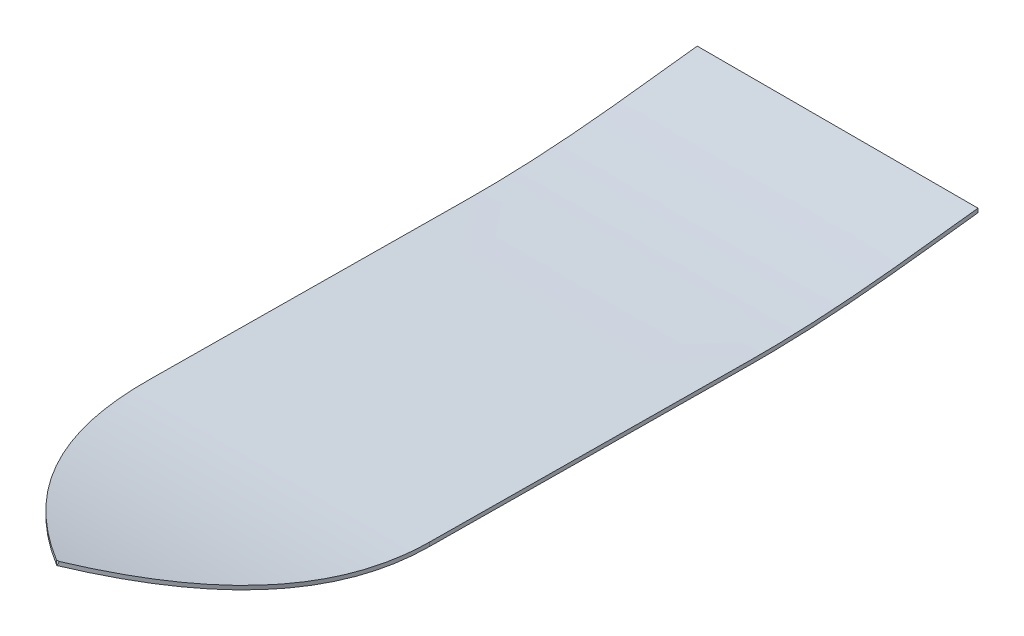
SolidWorks part; units mm, degrees
ref_plane "Front Plane" through (0, 0, 0) normal (0, 0, 1) x (1, 0, 0)
ref_plane "Top Plane" through (0, 0, 0) normal (0, 1, 0) x (1, 0, 0)
ref_plane "Right Plane" through (0, 0, 0) normal (1, 0, 0) x (0, 0, -1)
sketch "Sketch1" plane through (0, 0, 0) normal (1, 0, 0) x (0, 0, -1)
  line L6 (-3044.2698, 164.4803) -> (-3050.7389, 140.3318)
  line L7 (1954.9582, 71.8051) -> (1957.9009, 46.9789)
  spline S0 degree 3 poles (-3044.2698, 164.4803) (-2812.3217, 102.3436) (-2472.36, 36.8584) (-1994.9412, -9.8893) (-1747.6762, -21.1854) (-1597.5125, -23.4676) (-1563.2422, -23.7855) (-1460.4237, -24.7287) (-1282.2019, -26.3591) (-1001.1607, -28.9313) (-589.881, -32.6958) (-206.0199, -36.2092) (164.1318, -39.5971) (337.2119, -41.1813) (458.8794, -42.2934) (493.1569, -42.6094) (566.4691, -43.0811) (687.4943, -42.0008) (1179.1806, -25.7469) (1562.5379, 25.2909) (1954.9582, 71.8051) knots 0 0 0 0 0.15625 0.21875 0.289062 0.300781 0.304688 0.308594 0.359375 0.40625 0.46875 0.59375 0.625 0.679688 0.692383 0.694336 0.699219 0.734375 0.765625 1 1 1 1
  spline S1 degree 1 poles (-3050.7389, 140.3318) (1957.9009, 46.9789) knots 0 0 1 1 construction
  spline S2 degree 3 poles (-3050.7389, 140.3318) (-3039.0666, 137.2049) (-3015.7221, 131.043) (-2968.7594, 119.0132) (-2909.6691, 104.561) (-2838.1023, 88.1439) (-2741.8165, 67.4919) (-2619.8339, 43.9951) (-2470.8578, 19.5074) (-2319.285, -1.2734) (-2165.1165, -18.3484) (-2008.3529, -31.7191) (-1875.5546, -39.7757) (-1768.0188, -44.3698) (-1700.269, -46.4717) (-1645.7441, -47.6872) (-1604.6906, -48.3776) (-1563.4486, -48.7918) (-1522.3501, -49.1597) (-1481.2146, -49.5391) (-1426.3799, -50.0406) (-1330.4129, -50.9195) (-1193.3203, -52.1735) (-1028.8081, -53.6794) (-864.2963, -55.1851) (-699.7844, -56.6909) (-535.2725, -58.1966) (-370.7606, -59.7024) (-206.2488, -61.2081) (-41.7369, -62.7139) (95.3563, -63.9687) (205.031, -64.9725) (287.2863, -65.7252) (355.8337, -66.3524) (410.6675, -66.8536) (444.9472, -67.1675) (472.3507, -67.4179) (492.9632, -67.6114) (513.4929, -67.735) (540.7008, -67.8206) (574.4475, -67.7776) (627.8916, -67.3981) (693.7232, -66.3556) (771.325, -64.2438) (847.6955, -61.3194) (948.1, -56.4017) (1071.349, -48.4663) (1216.9541, -36.4721) (1361.5858, -22.3963) (1482.4051, -9.2564) (1579.9013, 1.9075) (1653.6106, 10.5581) (1728.0741, 19.438) (1790.8946, 26.9889) (1841.6962, 33.0963) (1880.0886, 37.7039) (1912.3506, 41.562) (1938.3133, 44.6544) (1951.3785, 46.2058) (1957.9009, 46.9789) knots 0 0 0 0 0.007812 0.015625 0.03125 0.046875 0.0625 0.09375 0.125 0.15625 0.1875 0.21875 0.25 0.265625 0.28125 0.289062 0.296875 0.304688 0.3125 0.320312 0.328125 0.34375 0.375 0.40625 0.4375 0.46875 0.5 0.53125 0.5625 0.59375 0.625 0.640625 0.65625 0.671875 0.679688 0.6875 0.691406 0.695312 0.699219 0.703125 0.710938 0.71875 0.734375 0.75 0.765625 0.78125 0.8125 0.84375 0.875 0.90625 0.921875 0.9375 0.953125 0.96875 0.976562 0.984375 0.992188 0.996094 1 1 1 1
  dimension "D1" = 25
extrude "Boss-Extrude1" add sketch "Sketch1" along normal blind 1524 and the other way blind 1524
sketch "Sketch3" plane through (0, 0, 0) normal (0, 1, 0) x (1, 0, 0)
  line L0 (-900, 1954.9582) -> (900, 1954.9582)
  line L1 (-900, 1954.9582) -> (-900, -1562.5754)
  line L2 (900, 1954.9582) -> (900, -1562.5754)
  line L3 (0, 2955.5244) -> (0, -2061.9995) construction
  line L4 (-1976.5237, 3461.0506) -> (3754.9336, 3461.0506)
  line L5 (-1976.5237, 3461.0506) -> (-1976.5237, -4542.2553)
  line L6 (-1976.5237, -4542.2553) -> (3754.9336, -4542.2553)
  line L7 (3754.9336, 3461.0506) -> (3754.9336, -4542.2553)
  line L8 (-94.9374, 0) -> (0, 0) construction
  line L11 (-1524, 1954.9582) -> (1524, 1954.9582) construction
  spline S0 degree 2 poles (-900, -1562.5754) (-900, -2437.214) (0, -3050.7389) knots 0 0 0 1 1 1
  spline S1 degree 2 poles (900, -1562.5754) (900, -2437.214) (0, -3050.7389) knots 0 0 0 1 1 1
  dimension "D1" = 1800
extrude "Cut-Extrude1" cut sketch "Sketch3" against normal through all both and the other way through all
